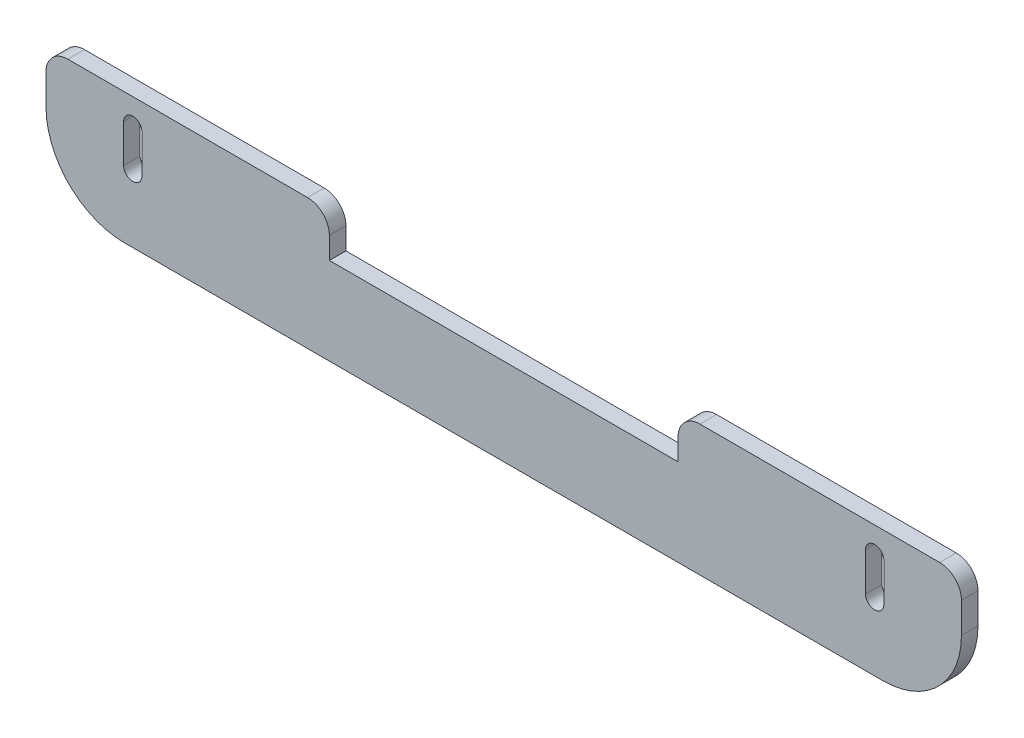
SolidWorks part; units mm, degrees
ref_plane "Front Plane" through (0, 0, 0) normal (0, 0, 1) x (1, 0, 0)
ref_plane "Top Plane" through (0, 0, 0) normal (0, 1, 0) x (1, 0, 0)
ref_plane "Right Plane" through (0, 0, 0) normal (1, 0, 0) x (0, 0, -1)
sketch "Sketch1" plane through (0, 0, 0) normal (0, 0, 1) x (1, 0, 0)
  line L0 (243.84, 0) -> (22.86, 0)
  line L1 (0, 0) -> (0, 6.35)
  line L2 (0, 22.86) -> (0, 31.75)
  line L3 (190.5, 38.1) -> (260.35, 38.1)
  line L4 (266.7, 31.75) -> (266.7, 22.86)
  line L5 (82.55, 25.4) -> (184.15, 25.4)
  line L6 (82.55, 25.4) -> (82.55, 31.75)
  line L7 (6.35, 38.1) -> (76.2, 38.1)
  line L8 (184.15, 25.4) -> (184.15, 31.75)
  line L11 (82.55, 25.4) -> (82.55, 31.75)
  arc A0 (260.35, 38.1) -> (266.7, 31.75) centre (260.35, 31.75) cw
  arc A1 (243.84, 0) -> (266.7, 22.86) centre (243.84, 22.86) ccw
  arc A2 (22.86, 0) -> (0, 22.86) centre (22.86, 22.86) cw
  arc A3 (6.35, 38.1) -> (0, 31.75) centre (6.35, 31.75) ccw
  arc A4 (190.5, 38.1) -> (184.15, 31.75) centre (190.5, 31.75) ccw
  arc A5 (76.2, 38.1) -> (82.55, 31.75) centre (76.2, 31.75) cw
  point P7 (253.9906, 35.9177)
  point P10 (266.7, 0)
  point P12 (266.7, 0)
  point P13 (0, 0)
  point P16 (0, 38.1)
  point P17 (133.35, 19.05)
  dimension "D3" = 6.35
  dimension "D4" = 6.35
  dimension "D7" = 22.86
  dimension "D1" = 254
  dimension "D2" = 38.1
  dimension "D5" = 101.6
  dimension "D6" = 133.35
extrude "Boss-Extrude1" add sketch "Sketch1" along normal blind 4.826 contours A5 L7 A3 L2 A1 A0 L3 A4 L8 L5 L6 region at (133.35, 17.4395, 0)
sketch "Sketch2" plane through (0, 0, 4.826) normal (0, 0, 1) x (1, 0, 0)
  line L0 (25.279, 30.5233) -> (25.279, 19.3532) construction
  line L1 (27.9446, 30.5233) -> (27.9446, 19.3532)
  line L2 (22.6134, 30.5233) -> (22.6134, 19.3532)
  line L3 (133.35, 25.4) -> (133.35, 0) construction
  line L4 (82.55, 25.4) -> (184.15, 25.4) construction
  line L5 (243.84, 0) -> (22.86, 0) construction
  line L6 (241.421, 30.5233) -> (241.421, 19.3532) construction
  line L7 (238.7554, 30.5233) -> (238.7554, 19.3532)
  line L8 (244.0866, 30.5233) -> (244.0866, 19.3532)
  line L9 (25.279, 30.5233) -> (25.279, 19.3532) construction
  arc A0 (27.9446, 30.5233) -> (22.6134, 30.5233) centre (25.279, 30.5233) ccw
  arc A1 (22.6134, 19.3532) -> (27.9446, 19.3532) centre (25.279, 19.3532) ccw
  arc A2 (238.7554, 30.5233) -> (244.0866, 30.5233) centre (241.421, 30.5233) cw
  arc A3 (244.0866, 19.3532) -> (238.7554, 19.3532) centre (241.421, 19.3532) cw
  point P2 (25.279, 24.9382)
  point P15 (241.421, 24.9382)
extrude "Cut-Extrude1" cut sketch "Sketch2" against normal through all
equation "\"MDF\"= 0.19in"
equation "\"PVCID\" = 2.067in"
equation "\"PVCOD\" = 2.375in"
equation "\"GenDiameter\"= 60mm"
equation "\"GenCutDiameter\" = 1.8in"
equation "\"GenCutDistance\" = 1"
equation "\"TowerHeight\" = 6in"
equation "\"TowerFrontBase\" = 3in"
equation "\"FunnelHeight\" = 1in"
equation "\"FunnelAngle\" = 20"
equation "\"TowerSideBase\" = 3in"
equation "\"TowerPanelLength\" = 2in"
equation "\"TowerPanelLeeway\" = 0.5in"
equation "\"BaseLength\" = 9in"
equation "\"BaseWidth\" = 10in"
equation "\"WheelHoleLength\" = 3.25in"
equation "\"WheelHoleWidth\" = 26mm"
equation "\"WheelHoleFromBack\" = 1.5in"
equation "\"DropLength\" = 1in"
equation "\"DropWidth\" = 8.5in"
equation "\"BumperWidth\" = 2in"
equation "\"SmallHexDiameter\" = 0.185in"
equation "\"SmallHexHeight\" = 0.701in"
equation "\"ScrewSize\" = 0.106in"
equation "\"BigHexDiameter\" = 0.251in"
equation "\"BigHexHeight\" = 0.374in"
equation "\"PCBThickness\" = 0.066in"
equation "\"ConnectorHeight\" = 0.517in"
equation "\"BoardHeight\" = 0.583in"
equation "\"UnoStackHeight\" = 1.351in"
equation "\"UnoStackWidth\" = 3.053in"
equation "\"UnoStackLength\" = 3.152in"
equation "\"HBridgeWidth\" = 1.797in"
equation "\"HBridgeLength\" = 2.236in"
equation "\"DSWidth\" = 1.820in"
equation "\"DSLength\" = 1.833in"
equation "\"StepperWidth\" = 1.799in"
equation "\"StepperLength\" = 2.248in"
equation "\"ULNWidth\" = 1.304in"
equation "\"ULNLength\" = 1.545in"
equation "\"VSwitchHeight\" = 0.392in"
equation "\"VSwitchWidth\" = 0.637in"
equation "\"VSwitchLength\" = 1.097in"
equation "\"SkateWheelDiameter\" = 80mm"
equation "\"SkateWheelThickness\" = 24mm"
equation "\"BaseDistance\" = 3in"
equation "\"DummyVar\" = 2in"
equation "\"D1@Boss-Extrude1\"=\"MDF\""
